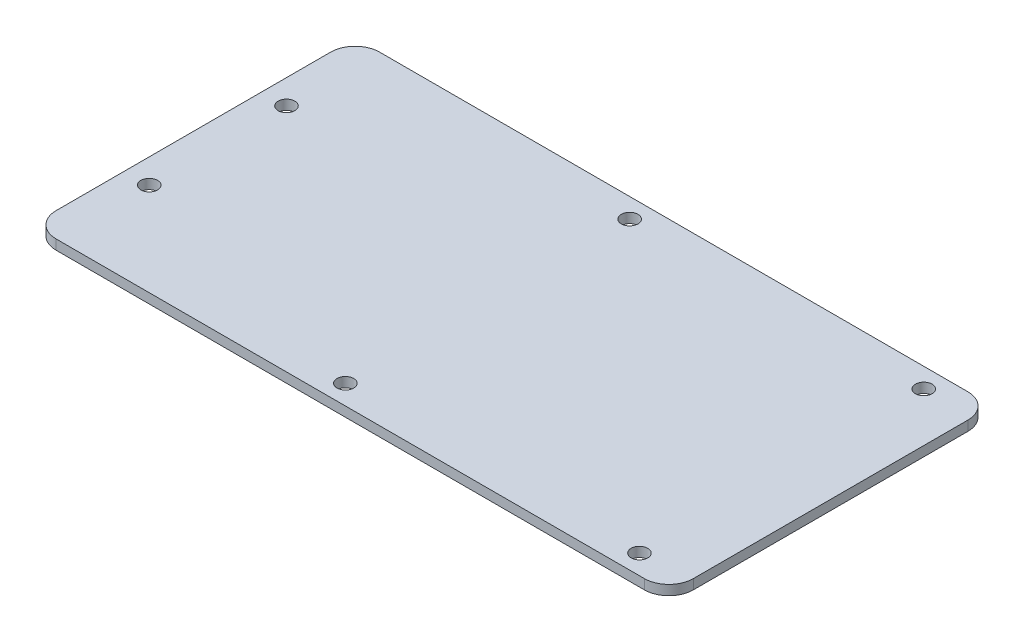
SolidWorks part; units mm, degrees
ref_plane "Front Plane" through (0, 0, 0) normal (0, 0, 1) x (1, 0, 0)
ref_plane "Top Plane" through (0, 0, 0) normal (0, 1, 0) x (1, 0, 0)
ref_plane "Right Plane" through (0, 0, 0) normal (1, 0, 0) x (0, 0, -1)
sketch "Sketch1" plane through (0, 0, 0) normal (0, 1, 0) x (1, 0, 0)
  line L1 (0, 0) -> (130, 0)
  line L2 (0, 0) -> (0, 66)
  line L3 (0, 66) -> (130, 66)
  line L4 (130, 0) -> (130, 66)
  dimension "D1" = 130
  dimension "D2" = 66
extrude "Boss-Extrude1" add sketch "Sketch1" along normal blind 2
fillet "Fillet1" radius 5 4 edges at (130, 1, -66) (130, 1, 0) (0, 1, 0) (0, 1, -66)
hole_wizard "M3 Clearance Hole1" positions "Sketch2" profile "Sketch3" hole size "M3" standard "ANSI Metric" end condition through all
sketch "Sketch2" plane through (0, 2, 0) normal (0, 1, 0) x (1, 0, 0)
  line L0 (0, 33) -> (156.4068, 33) construction
  line L1 (0, 61) -> (0, 5) construction
  line L3 (130, 5) -> (130, 61) construction
  point P0 (5, 19)
  point P2 (60, 4)
  point P4 (120, 4)
  point P16 (120, 62)
  point P17 (60, 62)
  point P18 (5, 47)
  dimension "D1" = 28
  dimension "D2" = 58
  dimension "D3" = 10
  dimension "D4" = 115
  dimension "D5" = 55
sketch "Sketch3" plane through (5, 2, -19) normal (1, 0, 0) x (0, 0, 1)
  line L0 (0, 0) -> (0, 2)
  line L1 (0, 2) -> (1.7, 2)
  line L2 (1.7, 2) -> (1.7, 0)
  line L5 (1.7, 0) -> (0, 0)
  line L11 (0, -6.35) -> (0, 107.95) construction
  dimension "Thru Hole Dia." = 3.4
  dimension "Thru Hole Depth" = 2
